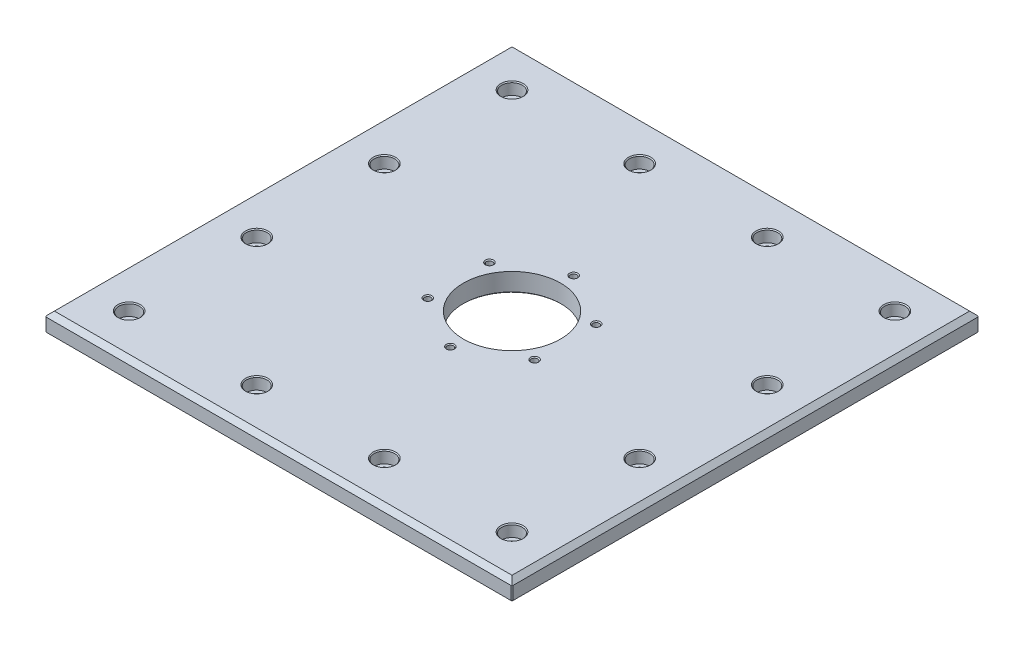
SolidWorks part; units mm, degrees
ref_plane "Ebene vorne" through (0, 0, 0) normal (0, 0, 1) x (1, 0, 0)
ref_plane "Ebene oben" through (0, 0, 0) normal (0, 1, 0) x (1, 0, 0)
ref_plane "Ebene rechts" through (0, 0, 0) normal (1, 0, 0) x (0, 0, -1)
sketch "Sketch1" plane through (0, 0, 0) normal (0, 1, 0) x (1, 0, 0)
  line L0 (0, -29) -> (0, -37) construction
  line L1 (-125, -125) -> (125, -125)
  line L2 (-125, -125) -> (-125, 125)
  line L3 (-125, 125) -> (125, 125)
  line L4 (125, -125) -> (125, 125)
  line L5 (-125, -125) -> (125, 125) construction
  line L6 (-125, 125) -> (125, -125) construction
  line L8 (-102.5, -102.5) -> (102.5, -102.5) construction
  line L9 (-102.5, -102.5) -> (-102.5, 102.5) construction
  line L10 (-102.5, 102.5) -> (102.5, 102.5) construction
  line L11 (102.5, -102.5) -> (102.5, 102.5) construction
  line L12 (-102.5, -102.5) -> (102.5, 102.5) construction
  line L13 (-102.5, 102.5) -> (102.5, -102.5) construction
  circle A0 centre (0, 0) radius 26
  circle A1 centre (0, 0) radius 29 construction
  circle A2 centre (0, 0) radius 37
  point P0 (0, 0)
  point P12 (0, -33)
  point P13 (-28.5788, -16.5)
  point P16 (-28.5788, 16.5)
  point P17 (0, 33)
  point P18 (28.5788, 16.5)
  point P19 (28.5788, -16.5)
  point P20 (0, 0)
  point P24 (-102.5, 102.5)
  point P27 (-34.1667, 102.5)
  point P28 (34.1667, 102.5)
  point P29 (102.5, 102.5)
  point P30 (-34.1667, 34.1667)
  point P31 (34.1667, 34.1667)
  point P32 (102.5, 34.1667)
  point P33 (-34.1667, -34.1667)
  point P34 (34.1667, -34.1667)
  point P35 (102.5, -34.1667)
  point P36 (-34.1667, -102.5)
  point P37 (34.1667, -102.5)
  point P38 (102.5, -102.5)
  point P39 (-102.5, 34.1667)
  point P40 (-102.5, -34.1667)
  point P41 (-102.5, -102.5)
  dimension "D2" = 52
  dimension "D3" = 58
  dimension "D4" = 8
  dimension "D1" = 250
  dimension "D5" = 6
  dimension "D6" = 205
  dimension "D7" = 4
  dimension "D8" = 4
extrude "Boss-Extrude1" add sketch "Sketch1" along normal blind 10 contours L1 L4 L3 L2 A2 | A2 A0 region at (-121.4645, 0, 0) region at (-35.9535, 0, 0)
hole_wizard "M3 Clearance Hole1" positions "Sketch2" profile "Sketch3" hole size "M3" standard "DIN" end condition through all
sketch "Sketch2" plane through (0, 10, 0) normal (0, 1, 0) x (1, 0, 0)
  point P0 (0, 33)
  point P3 (28.5788, 16.5)
  point P6 (28.5788, -16.5)
  point P9 (0, -33)
  point P12 (-28.5788, -16.5)
  point P15 (-28.5788, 16.5)
sketch "Sketch3" plane through (0, 10, -33) normal (1, 0, 0) x (0, 0, 1)
  line L0 (0, 0) -> (0, 10)
  line L1 (0, 10) -> (1.7, 10)
  line L2 (1.7, 10) -> (1.7, 0)
  line L5 (1.7, 0) -> (0, 0)
  line L11 (0, -6.35) -> (0, 107.95) construction
  dimension "Thru Hole Dia." = 3.4
  dimension "Thru Hole Depth" = 10
hole_wizard "CBORE for M6 Hex Socket Head Cap Screw1" positions "Sketch4" profile "Sketch5" counterbore size "M6" standard "DIN" end condition through all
sketch "Sketch4" plane through (0, 10, 0) normal (0, 1, 0) x (1, 0, 0)
  point P0 (-102.5, 102.5)
  point P3 (-34.1667, 102.5)
  point P6 (34.1667, 102.5)
  point P9 (102.5, 102.5)
  point P12 (102.5, 34.1667)
  point P15 (102.5, -34.1667)
  point P18 (102.5, -102.5)
  point P21 (34.1667, -102.5)
  point P24 (-34.1667, -102.5)
  point P27 (-102.5, -102.5)
  point P30 (-102.5, -34.1667)
  point P33 (-102.5, 34.1667)
sketch "Sketch5" plane through (-102.5, 10, -102.5) normal (1, 0, 0) x (0, 0, 1)
  line L0 (0, 0) -> (0, 10)
  line L1 (0, 10) -> (3.3, 10)
  line L3 (3.3, 10) -> (3.3, 6.4)
  line L4 (3.3, 6.4) -> (5.5, 6.4)
  line L5 (5.5, 6.4) -> (5.5, 0)
  line L7 (5.5, 0) -> (0, 0)
  line L11 (0, -6.35) -> (0, 107.95) construction
  dimension "Thru Hole Dia." = 6.6
  dimension "Thru Hole Depth" = 10
  dimension "C'Bore Dia." = 11
  dimension "C'Bore Depth" = 6.4
chamfer "2,5mm Chamfer1" distance 2.5 angle 45 4 edges at (-125, 10, 0) (0, 10, -125) (125, 10, 0) (0, 10, 125)
chamfer "0,5mm Chamfer2" distance 0.5 angle 45 45 edges at (0, 0, 26) (-28.5788, 0, -14.8) (-28.5788, 0, 18.2) (0, 0, 34.7) (28.5788, 0, 18.2) (28.5788, 0, -14.8) (0, 0, -31.3) (-102.5, 0, -30.8667) (-102.5, 0, 37.4667) (-102.5, 0, 105.8) (-34.1667, 0, 105.8) (34.1667, 0, 105.8) (102.5, 0, 105.8) (102.5, 0, 37.4667) (102.5, 0, -30.8667) (102.5, 0, -99.2) (34.1667, 0, -99.2) (-34.1667, 0, -99.2) (-102.5, 0, -99.2) (-28.5788, 10, -14.8) (0, 10, -31.3) (-28.5788, 10, 18.2) (0, 10, 34.7) (28.5788, 10, 18.2) (28.5788, 10, -14.8) (34.1667, 10, -97) (-34.1667, 10, -97) (-102.5, 10, -97) (-102.5, 10, -28.6667) (-102.5, 10, 39.6667) (-102.5, 10, 108) (-34.1667, 10, 108) (34.1667, 10, 108) (102.5, 10, -28.6667) (102.5, 10, -97) (102.5, 10, 39.6667) (102.5, 10, 108) (125, 0, 0) (125, 3.75, 125) (0, 0, 125) (-125, 3.75, 125) (-125, 0, 0) (-125, 3.75, -125) (0, 0, -125) (125, 3.75, -125)
